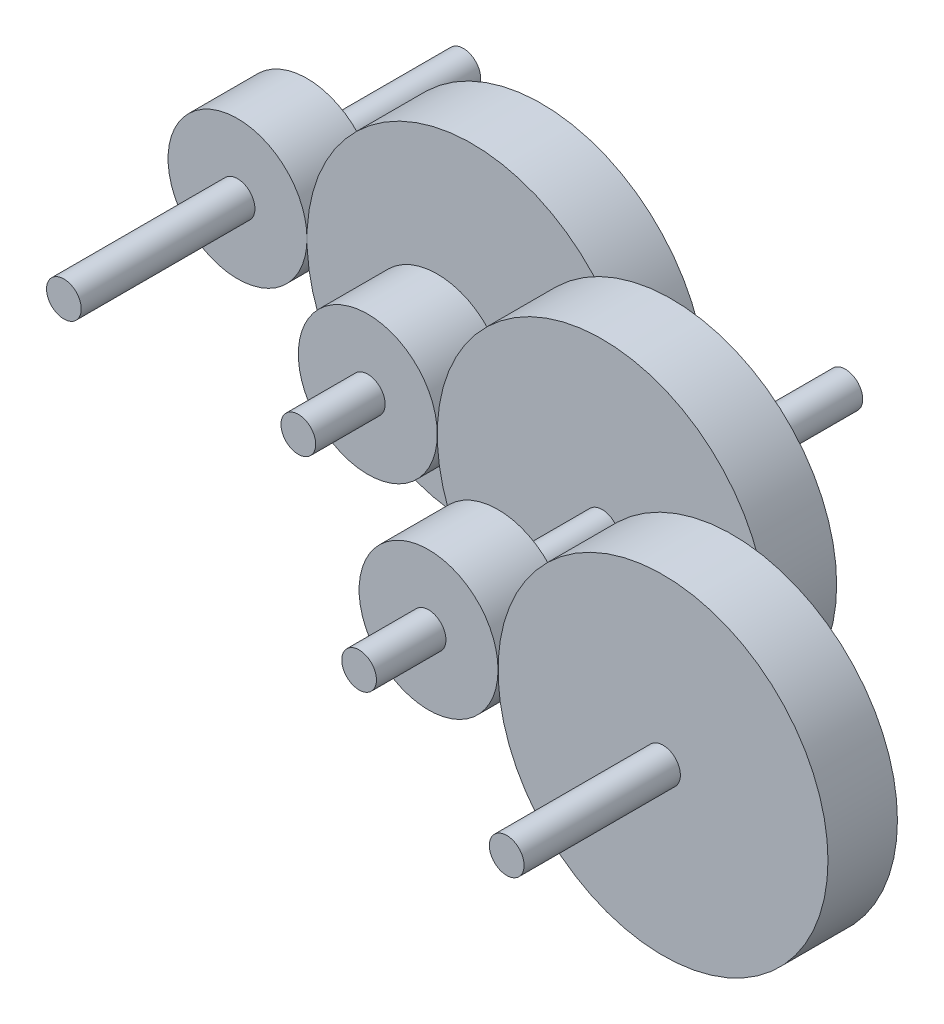
SolidWorks part; units mm, degrees
ref_plane "Front Plane" through (0, 0, 0) normal (0, 0, 1) x (1, 0, 0)
ref_plane "Top Plane" through (0, 0, 0) normal (0, 1, 0) x (1, 0, 0)
ref_plane "Right Plane" through (0, 0, 0) normal (1, 0, 0) x (0, 0, -1)
sketch "Sketch1" plane through (0, 0, 0) normal (0, 0, 1) x (1, 0, 0)
  line L1 (0, 0) -> (171.45, 0) construction
  line L2 (171.45, 0) -> (342.9, 0) construction
  line L3 (342.9, 0) -> (514.35, 0) construction
  circle A0 centre (0, 0) radius 12.7
  circle A1 centre (171.45, 0) radius 12.7
  circle A2 centre (342.9, 0) radius 12.7
  circle A3 centre (514.35, 0) radius 12.7
  circle A4 centre (0, 0) radius 50.8
  circle A5 centre (171.45, 0) radius 120.65
  circle A7 centre (171.45, 0) radius 50.8
  circle A8 centre (342.9, 0) radius 120.65
  circle A9 centre (342.9, 0) radius 50.8
  circle A10 centre (514.35, 0) radius 120.65
  circle A11 centre (0, 0) radius 38.1
  circle A12 centre (171.45, 0) radius 38.1
  circle A13 centre (342.9, 0) radius 38.1
  circle A14 centre (514.35, 0) radius 38.1
  dimension "D1" = 25.4
  dimension "D2" = 25.4
  dimension "D5" = 25.4
  dimension "D8" = 25.4
  dimension "D11" = 101.6
  dimension "D12" = 241.3
  dimension "D13" = 76.2
  dimension "D3" = 171.45
  dimension "D6" = 171.45
  dimension "D10" = 171.45
extrude "Boss-Extrude1" add sketch "Sketch1" along normal blind 292.1 contours A0
extrude "Boss-Extrude2" add sketch "Sketch1<3>" along normal blind 228.6 from offset 63.5 separate body contours A1
sketch "Sketch1<3>" plane through (0, 0, 0) normal (0, 0, 1) x (1, 0, 0) same geometry as "Sketch1"
extrude "Boss-Extrude3" add sketch "Sketch1<4>" along normal blind 355.6 from offset 63.5 separate body contours A2
sketch "Sketch1<4>" plane through (0, 0, 0) normal (0, 0, 1) x (1, 0, 0) same geometry as "Sketch1"
extrude "Boss-Extrude4" add sketch "Sketch1<5>" along normal blind 215.9 from offset 266.7 separate body contours A3
sketch "Sketch1<5>" plane through (0, 0, 0) normal (0, 0, 1) x (1, 0, 0) same geometry as "Sketch1"
extrude "Boss-Extrude5" add sketch "Sketch1<6>" along normal blind 50.8 from offset 114.3 separate body contours A4 A11 | A11 A0 | A8 A5 A7 | A7 A12 | A12 A1 | A5 A8 region at (-49.3632, 0, 0) region at (122.0868, 0, 0) region at (126.7575, 108.6412, 0) region at (257.175, 0, 0) region at (-37.0224, 0, 0) region at (134.4276, 0, 0)
sketch "Sketch1<6>" plane through (0, 0, 0) normal (0, 0, 1) x (1, 0, 0) same geometry as "Sketch1"
extrude "Boss-Extrude7" add sketch "Sketch1<9>" along normal blind 50.8 from offset 190.5 contours A7 | A8
sketch "Sketch1<9>" plane through (0, 0, 0) normal (0, 0, 1) x (1, 0, 0) same geometry as "Sketch1"
extrude "Boss-Extrude8" add sketch "Sketch1<10>" along normal blind 50.8 from offset 317.5 contours A8 A10 A3 | A8 A10 | A14 A3 | A9 | A3 region at (559.0425, 108.6412, 0) region at (428.625, 0, 0) region at (477.3276, 0, 0)
sketch "Sketch1<10>" plane through (0, 0, 0) normal (0, 0, 1) x (1, 0, 0) same geometry as "Sketch1"
equation "\"D12@Sketch1\"=\"NG\"/\"DP\""
equation "\"D11@Sketch1\"=\"NP\"/\"DP\""
equation "\"D8@Sketch1\"=\"d\""
equation "\"D2@Sketch1\"=\"d\""
equation "\"NP\"= 16"
equation "\"NG\"= 38"
equation "\"DP\"= 4'diametrial pitch"
equation "\"angleAB\"= 0"
equation "\"angleBC\"= 0"
equation "\"angleCD\"= 0"
equation "\"F\" = 2'gear face width"
equation "\"S\"= 1'shoulder axial length"
equation "\"B\"= 1'bearing axial length"
equation "\"d\"= 1'shaft diameter"
equation "\"E\"= 2.5'length of shaft outside gearbox"
equation "\"shoulderD\" = 3'shoulder diameter"
equation "\"D1@Boss-Extrude1\"=\"l_a\""
equation "\"CtoC\"= ( \"NP\" + \"NG\" ) / 2 / \"DP\""
equation "\"l_b\"= 2 * \"B\" + \"S\" * 3 + \"F\" * 2"
equation "\"l_a\"= \"l_b\" + \"E\""
equation "\"l_c\"= \"l_b\" + \"S\" * 2 + \"F\" + \"B\""
equation "\"l_d\"= \"B\" * 2 + 2 * \"S\" + \"F\" + \"E\""
equation "\"D3@Sketch1\"=\"CtoC\""
equation "\"D5@Sketch1\"=\"d\""
equation "\"D6@Sketch1\"=\"CtoC\""
equation "\"D10@Sketch1\"=\"CtoC\""
equation "\"D1@Boss-Extrude2\"=\"l_b\""
equation "\"D1@Boss-Extrude3\"=\"l_c\""
equation "\"D19@Boss-Extrude4\"=\"l_a\"-\"B\""
equation "\"D19@Boss-Extrude2\"=\"E\""
equation "\"D19@Boss-Extrude5\"=\"E\"+\"B\"+\"S\""
equation "\"D19@Boss-Extrude7\"=\"E\"+\"S\"+\"F\"+\"S\"+\"B\""
equation "\"D1@Boss-Extrude7\"=\"F\""
equation "\"D19@Boss-Extrude8\"=\"E\"+2*\"B\"+4*\"S\"+2*\"F\""
equation "\"D1@Boss-Extrude8\"=\"F\""
equation "\"D1@Boss-Extrude4\"=\"l_d\""
equation "\"D13@Sketch1\"=\"shoulderD\""
equation "\"D19@Boss-Extrude3\"=\"E\""
